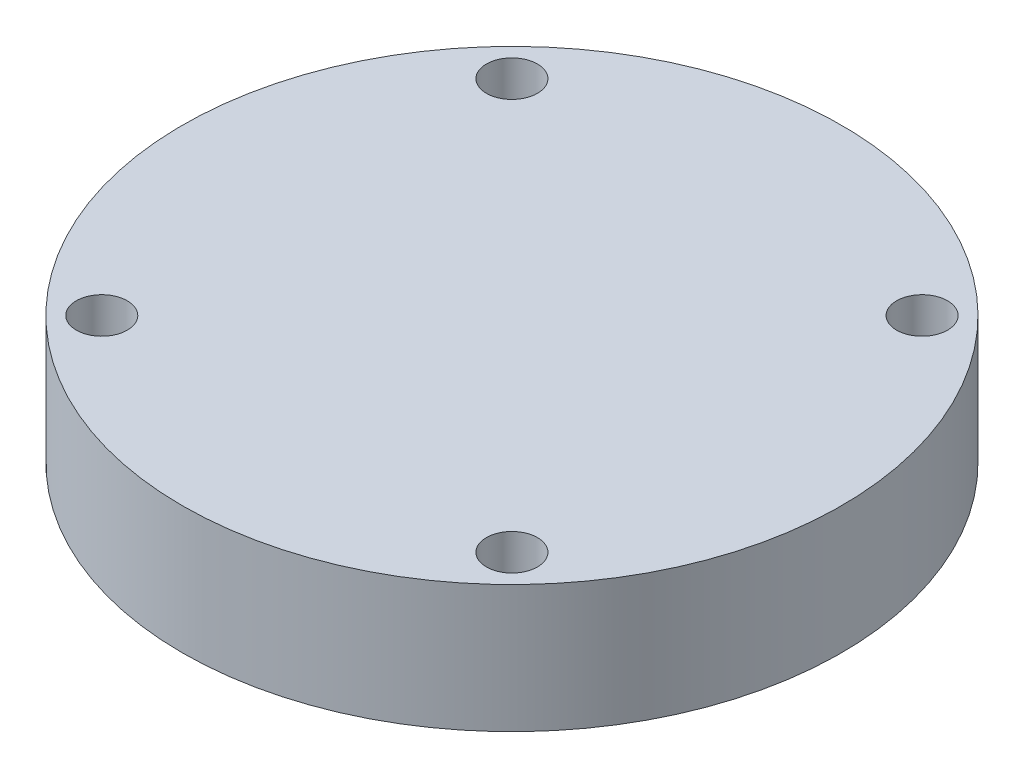
SolidWorks part; units mm, degrees
material "1060 Alloy"
ref_plane "Front Plane" through (0, 0, 0) normal (0, 0, 1) x (1, 0, 0)
ref_plane "Top Plane" through (0, 0, 0) normal (0, 1, 0) x (1, 0, 0)
ref_plane "Right Plane" through (0, 0, 0) normal (1, 0, 0) x (0, 0, -1)
ref_axis "Y Axis" through (0, 7.7343, 0) along (0, -1, 0)
sketch "outer" plane through (0, 0, 0) normal (0, 1, 0) x (1, 0, 0)
  circle A0 centre (0, 0) radius 19.05
  dimension "D1" = 38.1
extrude "Body" add sketch "outer" along normal blind 7.366
sketch "inner" plane through (0, 0, 0) normal (0, 1, 0) x (1, 0, 0)
  circle A0 centre (0, 0) radius 11.811
  dimension "D1" = 23.622
extrude "Pocket" cut sketch "inner" along normal blind 4.826
sketch "Screw Position" plane through (0, 0, 0) normal (0, 1, 0) x (1, 0, 0)
  point P0 (-11.8539, 11.8539)
  dimension "D1" = 16.764
hole_wizard "#4 Clearance Hole1" positions "Sketch7" profile "Sketch8" hole size "#4" standard "ANSI Inch" end condition through all
sketch "Sketch7" plane through (0, 7.366, 0) normal (0, 1, 0) x (1, 0, 0)
  point P0 (-11.8539, 11.8539)
sketch "Sketch8" plane through (-11.8539, 7.366, -11.8539) normal (1, 0, 0) x (0, 0, 1)
  line L0 (0, 0) -> (0, 7.366)
  line L1 (0, 7.366) -> (1.4732, 7.366)
  line L2 (1.4732, 7.366) -> (1.4732, 0)
  line L5 (1.4732, 0) -> (0, 0)
  line L11 (0, -6.35) -> (0, 107.95) construction
  dimension "Thru Hole Dia." = 2.9464
  dimension "Thru Hole Depth" = 7.366
pattern_circular "Screw Holes" count 4 over 360 about axis through (0, 7.7343, 0) along (0, -1, 0) of "#4 Clearance Hole1"
sketch "Post Sketch" plane through (0, 0, 0) normal (0, 1, 0) x (1, 0, 0)
  circle A0 centre (0, -5.715) radius 1.0033
  circle A1 centre (5.2984, -5.2984) radius 1.0033
  point P0 (0, -5.715)
  point P1 (5.2984, -5.2984)
  dimension "D3" = 2.0066
  dimension "D4" = 2.0066
  dimension "D1" = 5.715
extrude "Post" add sketch "Post Sketch" against normal blind 4.826 from surface starting at face at (0, 4.826, 11.811)
pattern_circular "Posts" count 4 over 360 about axis through (0, 7.7343, 0) along (0, -1, 0) of "Post"
sketch "Flat Cut Sketch" plane through (0, 0, 0) normal (0, 1, 0) x (1, 0, 0)
  line L0 (0, 19.05) -> (0, -19.05) construction
  line L1 (-17.78, 19.05) -> (-20.32, -19.05) construction
  line L2 (17.78, -19.05) -> (20.32, -19.05)
  line L3 (17.78, -19.05) -> (17.78, 19.05)
  line L4 (17.78, 19.05) -> (20.32, 19.05)
  line L5 (20.32, -19.05) -> (20.32, 19.05)
  line L6 (17.78, -19.05) -> (20.32, 19.05) construction
  line L7 (17.78, 19.05) -> (20.32, -19.05) construction
  line L8 (-17.78, -19.05) -> (-20.32, 19.05) construction
  line L9 (-20.32, -19.05) -> (-20.32, 19.05)
  line L10 (-17.78, 19.05) -> (-20.32, 19.05)
  line L11 (-17.78, -19.05) -> (-17.78, 19.05)
  line L12 (-17.78, -19.05) -> (-20.32, -19.05)
  circle A0 centre (0, 0) radius 19.05 construction
  point P5 (19.05, 0)
  point P14 (-19.05, 0)
  dimension "D1" = 38.1
  dimension "D2" = 2.54
extrude "Flat Cut" [suppressed] cut sketch "Flat Cut Sketch" along normal through all
equation "\"outer_d\"= 3 / 2in"
equation "\"top_h\"= 1 / 4in"
equation "\"screw_r\"= 0.66in"
equation "\"inner_d\"= 0.93in"
equation "\"inner_h\"= 150mil"
equation "\"D1@outer\" = \"outer_d\""
equation "\"D1@Body\"=\"top_h\" + \"inset_h\""
equation "\"D1@inner\"=\"inner_d\""
equation "\"D1@Pocket\"=\"inner_h\" + \"inset_h\""
equation "\"D1@Screw Position\"=\"screw_r\""
equation "\"post_r1\"= 0.225in"
equation "\"post_r2\"= 0.295in"
equation "\"post_bottom_h\"= 0.04in"
equation "\"D1@Post Sketch\" = \"post_r1\""
equation "\"D2@Post Sketch\" = \"post_r2\""
equation "\"post_d\"= 0.079in"
equation "\"D3@Post Sketch\"=\"post_d\""
equation "\"D4@Post Sketch\"=\"post_d\""
equation "\"D1@Post\" = \"inner_h\" + \"post_bottom_h\""
equation "\"inset_h\"= 0.04in"
equation "\"D1@Flat Cut Sketch\" = \"outer_d\""
equation "\"flat_cut\"= 0.05in"
equation "\"D2@Flat Cut Sketch\" = \"flat_cut\" * 2"
